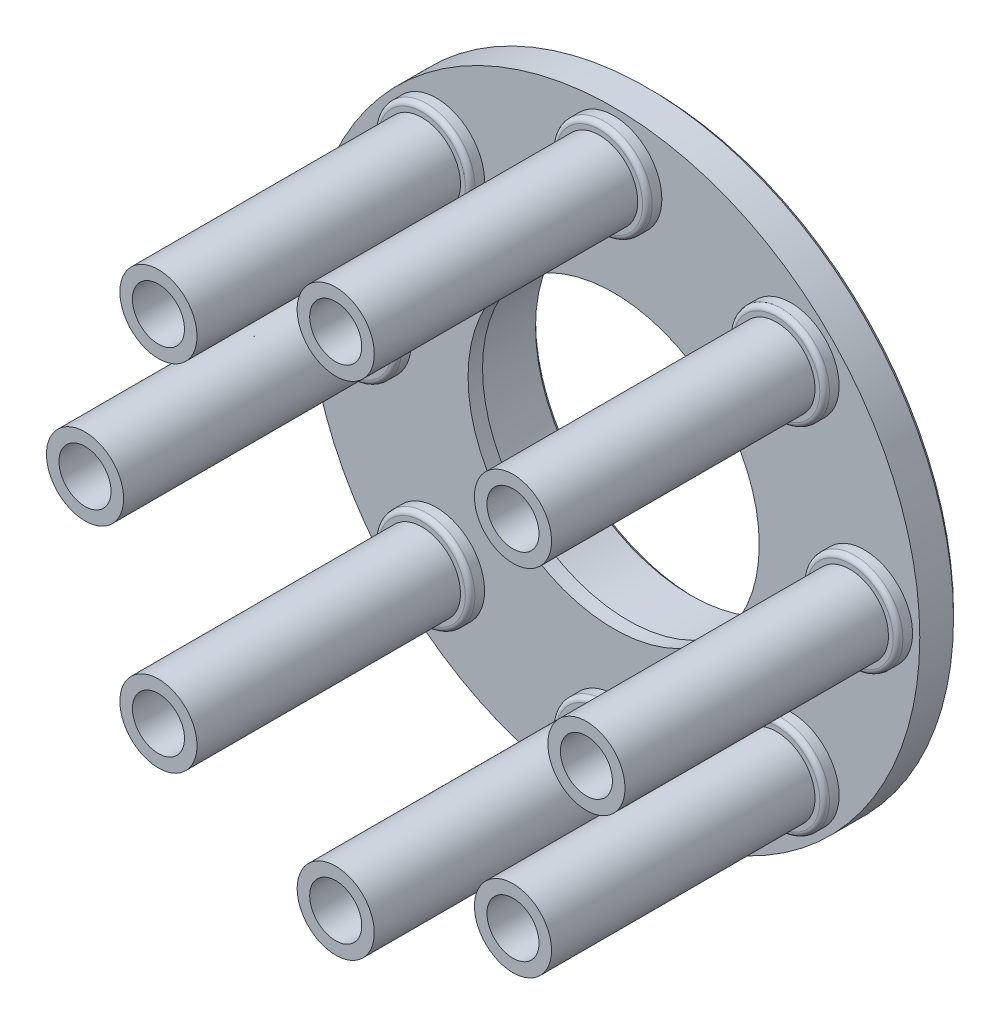
SolidWorks part; units mm, degrees
material "PLA"
ref_plane "Front Plane" through (0, 0, 0) normal (0, 0, 1) x (1, 0, 0)
ref_plane "Top Plane" through (0, 0, 0) normal (0, 1, 0) x (1, 0, 0)
ref_plane "Right Plane" through (0, 0, 0) normal (1, 0, 0) x (0, 0, -1)
sketch "Sketch1" plane through (0, 0, 0) normal (0, 0, 1) x (1, 0, 0)
  circle A0 centre (0, 0) radius 31.75
  circle A1 centre (0, 0) radius 26 construction
  circle A2 centre (0, 26) radius 2.7
  circle A3 centre (26, 0) radius 2.7
  circle A78 centre (0, -26) radius 2.7
  circle A79 centre (0, 26) radius 4.25 construction
  circle A80 centre (0, 0) radius 30.25 construction
  circle A87 centre (-26, 0) radius 2.7
  point P15 (0, 0)
  dimension "D2" = 52
  dimension "D3" = 5.4
  dimension "D5" = 8.5
  dimension "D1" = 1.5
  dimension "D4" = 4
extrude "Boss-Extrude1" add sketch "Sketch1" along normal blind 4
sketch "Sketch2" plane through (0, 0, 4) normal (0, 0, 1) x (1, 0, 0)
  circle A0 centre (0, 26) radius 4
  circle A2 centre (0, 26) radius 2.7 construction
  circle A5 centre (0, 26) radius 2.7
  point P15 (0, 0)
  dimension "D1" = 8
extrude "Boss-Extrude2" add sketch "Sketch2" along normal blind 28.8234
sketch "Sketch3" plane through (0, 0, 4) normal (0, 0, 1) x (1, 0, 0)
  arc A2 (5, 26) -> (5, 26) centre (0, 26) ccw
  circle A3 centre (0, 26) radius 5
  circle M5 centre (0, 26) radius 4
extrude "Boss-Extrude3" add sketch "Sketch3" along normal blind 1.5 contours A3 M5 region at (-4.8586, 26, 4)
sketch "Sketch4" plane through (0, 0, 4) normal (0, 0, 1) x (1, 0, 0)
  line L0 (0, 0) -> (-22.4506, 22.4506) construction
  line L1 (0, 0) -> (0, 26) construction
  circle A0 centre (0, 0) radius 31.75 construction
  circle A1 centre (0, 0) radius 31.75
  circle A2 centre (0, 26) radius 12 construction
  circle A6 centre (0, 0) radius 26 construction
  arc A8 (-13.189, 28.881) -> (-9.5294, 16.4375) centre (0, 26) ccw
  circle A9 centre (0, 0) radius 19
  circle A11 centre (0, 0) radius 14 construction
  arc A13 (-28.881, 13.189) -> (-16.4375, 9.5294) centre (-26, 0) cw
  circle A16 centre (0, 26) radius 13.5 construction
  point P15 (0, 0)
  point P25 (0, 0)
  dimension "D1" = 24
  dimension "D5" = 28
  dimension "D4" = 5
  dimension "D2" = 45
  dimension "D3" = 1.5
extrude "Boss-Extrude4" [suppressed] add sketch "Sketch4" along normal blind 28.8234 contours A1 A13 A9 A8
sketch "Sketch12" [suppressed] plane through (0, 0, 37.8382) normal (0, 0, 1) x (1, 0, 0)
  arc A0 (-11.2345, 15.816) -> (-15.816, 11.2345) centre (0, 0) ccw construction
  arc A1 (-11.2345, 15.816) -> (-15.816, 11.2345) centre (0, 0) ccw
  dimension "D1" = 6.4791
fillet "Fillet2" radius 0.5 1 edges at (5, 26, 5.5)
fillet "Fillet5" [suppressed] radius 1.6198
pattern_circular "CirPattern1" count 8 over 360 about axis through (0, 0, 4) along (0, 0, -1) of "Fillet2", "Boss-Extrude3", "Boss-Extrude2" reverse direction yes
ref_plane "Plane1" through (0, 0, 32.8234) normal (0, 0, 1) x (1, 0, 0)
chamfer "Chamfer1" distance 0.5 angle 45 1 edges at (31.75, 0, 0)
sketch "Sketch9" plane through (0, 0, 4) normal (0, 0, 1) x (1, 0, 0)
  circle A0 centre (0, 0) radius 8
  dimension "D1" = 16
extrude "Cut-Extrude4" cut sketch "Sketch9" against normal through all
sketch "Sketch10" plane through (0, 0, 0) normal (0, 0, -1) x (-1, 0, 0)
  circle A0 centre (0, 0) radius 8 construction
  circle A1 centre (0, 0) radius 8
  circle A2 centre (0, 0) radius 6.5
  dimension "D1" = 1.5
extrude "Boss-Extrude7" add sketch "Sketch10" against normal blind 6.5
sketch "Sketch13" plane through (0, 0, 0) normal (0, 1, 0) x (1, 0, 0)
  line L0 (0, 0) -> (0, -32.8234) construction
  line L1 (-4, -32.8234) -> (4, -32.8234) construction
  line L2 (15.6848, -4) -> (21.0848, -4) construction
  line L3 (-30, 0.5) -> (-38, -4) construction
  line L4 (-34.9404, -4) -> (-27.8293, 0)
  line L7 (31.25, 0) -> (-31.25, 0) construction
  line L8 (0, -4) -> (-38, -4) construction
  line L9 (-27.8293, 0) -> (-34.9404, 0)
  line L10 (-34.9404, 0) -> (-34.9404, -4)
  dimension "D1" = 30
  dimension "D2" = 38
  dimension "D3" = 4.5
  dimension "D4" = 1.5
sketch "Sketch14" plane through (0, 0, 4) normal (0, 0, 1) x (1, 0, 0)
  circle A0 centre (0, 0) radius 16.1
  circle A1 centre (0, 0) radius 6.5 construction
  dimension "D1" = 32.2
extrude "Cut-Extrude5" cut sketch "Sketch14" against normal through all both and the other way through all
sketch "Sketch15" plane through (0, 0, 4) normal (0, 0, 1) x (1, 0, 0)
  circle A0 centre (0, 0) radius 16.1
  circle A1 centre (0, 0) radius 15.1
  circle A2 centre (0, 0) radius 16.1 construction
  dimension "D1" = 1
extrude "Boss-Extrude8" add sketch "Sketch15" against normal blind 1.5
sketch "Sketch16" plane through (0, 0, 0) normal (0, 0, -1) x (-1, 0, 0)
  circle A0 centre (0, 0) radius 18.1
  circle A1 centre (0, 0) radius 16.1 construction
  circle M1 centre (0, 0) radius 16.1
extrude "Boss-Extrude9" add sketch "Sketch16" along normal blind 4.5 contours A0 M1 region at (17.5881, 0, 0)
chamfer "Chamfer3" distance 2 distance2 4.5 1 edges at (18.1, 0, 0) first distance on face at (18.1, 0, 0)
sketch "Sketch5" [suppressed] plane through (0, 0, 32.8234) normal (0, 0, 1) x (1, 0, 0)
  line L0 (0, 0) -> (-22.4506, 22.4506) construction
  line L1 (0, 0) -> (0, 26) construction
  circle A3 centre (-19.6222, 19.6222) radius 1.7
  circle A4 centre (0, 0) radius 31.75 construction
  arc A5 (-13.189, 28.881) -> (-28.881, 13.189) centre (0, 0) ccw construction
  dimension "D2" = 3.4
  dimension "D1" = 4
  dimension "D3" = 45
extrude "Cut-Extrude1" [suppressed] cut sketch "Sketch5" against normal through all
sketch "Sketch7" plane through (0, 0, 0) normal (0, 0, -1) x (-1, 0, 0)
  circle A0 centre (0, 26) radius 4.45
  circle A1 centre (0, 0) radius 26 construction
  point P15 (0, 0)
  dimension "D1" = 8.9
extrude "Cut-Extrude3" cut sketch "Sketch7" against normal blind 5 and the other way through all
sketch "Sketch6" [suppressed] plane through (0, 0, 0) normal (0, 0, -1) x (-1, 0, 0)
  circle A0 centre (19.6222, 19.6222) radius 2.95
  dimension "D1" = 5.9
extrude "Cut-Extrude2" [suppressed] cut sketch "Sketch6" against normal blind 3 and the other way through all
pattern_circular "CirPattern2" count 8 over 360 about axis through (0, 0, 4) along (0, 0, -1) of "Cut-Extrude3" reverse direction yes
chamfer "Chamfer4" distance 0.5 angle 45 1 edges at (-16.1, 0, -4.5)
equation "\"Nr_s\" = 132"
equation "\"module\" = 0.5"
equation "\"pressure_angle\" = 20.0"
equation "\"h_a\" = 0.5"
equation "\"h_f\" = 0.625"
equation "\"clr_tip_root\" = 0.125"
equation "\"dp_r_s\" = 66.0"
equation "\"db_r\"= \"dp_r_s\" * cos ( \"pressure_angle\" )'base CD"
equation "\"bearing_ID\" = 60"
equation "\"bearing_OD\" = 78"
equation "\"bearing_height\" = 10"
equation "\"clearance_planet\" = 1.5"
equation "\"case_dist\" = 6.5"
equation "\"Motor_case_OD_max\" = 111.3"
equation "\"case_mounting_PCD\" = 103.8"
equation "\"bearing mount thickness\" = 8"
equation "\"case_mounting_hole_dia\" = 3"
equation "\"output_mounting_PCD\" = 86"
equation "\"output_mounting_hole_dia\" = 4"
equation "\"clearance_case_mount_holes_shell_thickness\" = 1"
equation "\"motor_case_OD_base\" = 101.8"
equation "\"sec_carrier_thickness\" = 5"
equation "\"sun_coupler_hub_thickness\" = 4"
equation "\"clearance_sun_coupler_sec_carrier\" = 1.5"
equation "\"clearance_motor_and_case\" = 5"
equation "\"motor_OD\" = 86.8"
equation "\"Motor_case_thickness\" = 2.5"
equation "\"Motor_case_ID\" = 96.8"
equation "\"case_mounting_hole_shift\" = 1.0"
equation "\"output_mounting_nut_wrench_size\" = 7"
equation "\"output_mounting_nut_thickness\" = 3.2"
equation "\"case_mounting_hole_allen_socket_dia\" = 5.5"
equation "\"output_mounting_nut_depth\" = 3"
equation "\"case_mounting_bolt_depth\" = 4.5"
equation "\"Ns\" = 56"
equation "\"Np_b\" = 48"
equation "\"ring_radial_thickness\" = 5"
equation "\"ring_OD\"= \"Nr_s\" * \"module\" + \"ring_radial_thickness\" * 2"
equation "\"ring_to_chamfer_clearance\" = 1.5"
equation "\"Motor_case_OD_base_to_chamfer\" = 5"
equation "\"pattern_offset_from_motor_case_OD_base\" = 3"
equation "\"pattern_bulge_dia\" = 3"
equation "\"pattern_num_bulge\" = 18"
equation "\"pattern_depth\" = 2"
equation "\"motor_height\" = 26.5"
equation "\"case_mounting_wrench_size\" = 5.5"
equation "\"case_mounting_nut_clearance\" = 2"
equation "\"base_plate_thickness\" = 4"
equation "\"case_mounting_nut_thickness\" = 2.4"
equation "\"case_mounting_surface_height\" = 4"
equation "\"motor_mount_hole_PCD\" = 32"
equation "\"motor_mount_hole_dia\" = 4"
equation "\"motor_mount_hole_num\" = 4"
equation "\"central_hole_offset_from_motor_mount_PCD\" = 5"
equation "\"wire_slot_dist_from_center\" = 38"
equation "\"wire_slot_length\" = 10"
equation "\"wire_slot_radius\" = 2.5"
equation "\"driver_upper_holes_dist_from_center\" = 29"
equation "\"driver_lower_holes_dist_from_center\" = 13"
equation "\"driver_side_holes_dist_from_center\" = 22.5"
equation "\"driver_mount_holes_dia\" = 3"
equation "\"driver_mount_inserts_OD\" = 4.8"
equation "\"driver_mount_thickness\" = 1.5"
equation "\"driver_mount_height\" = 6"
equation "\"air_flow_hole_offset\" = 3"
equation "\"num_planet\" = 4"
equation "\"planet_pin_bolt_dia\" = 5"
equation "\"planet_pin_socket_head_dia\" = 8.5"
equation "\"carrier_PCD\" = 52.0"
equation "\"D2@Sketch1\"=\"carrier_PCD\""
equation "\"D3@Sketch1\"=\"planet_pin_bolt_dia\" + \"tight_clearance_3DP\""
equation "\"D4@Sketch1\"=\"num_planet\""
equation "\"D1@Boss-Extrude2\" = \"fw_p_s\" + \"clearance_planet\" * 2 + \"fw_p_b\""
equation "\"D1@Boss-Extrude3\"=\"clearance_planet\""
equation "\"D1@Sketch4\"=\"Np_b\"*\"module\""
equation "\"D3@Sketch4\"=\"clearance_planet\""
equation "\"D1@Boss-Extrude4\" = \"fw_p_s\" + \"clearance_planet\" * 2 + \"fw_p_b\""
equation "\"D1@Fillet2\"=\"clearance_planet\"/3"
equation "\"D1@CirPattern1\"=2*\"num_planet\""
equation "\"D1@CirPattern2\"=2*\"num_planet\""
equation "\"D1@Boss-Extrude7\"=\"bearing_height\"+ \"carrier_bearing_step_width\" - \"sun_shaft_bearing_width\""
equation "\"planet_shaft_dia\" = 8"
equation "\"D1@Sketch2\"= \"planet_shaft_dia\""
equation "\"planet_shaft_step_offset\" = 1"
equation "\"D1@Sketch3\"=\"planet_shaft_step_offset\""
equation "\"carrier_trapezoidal_support_sun_offset\" = 5"
equation "\"D4@Sketch4\"=\"carrier_trapezoidal_support_sun_offset\""
equation "\"carrier_trapezoidal_support_hole_PCD_offset_bearing_ID\" = 4"
equation "\"carrier_trapezoidal_support_hole_dia\" = 3"
equation "\"D2@Sketch5\"=\"carrier_trapezoidal_support_hole_dia\" + \"tight_clearance_3DP\""
equation "\"D1@Cut-Extrude2\"=\"carrier_trapezoidal_support_hole_dia\""
equation "\"carrier_trapezoidal_support_hole_socket_head_dia\" = 5.5"
equation "\"D1@Sketch6\"=\"carrier_trapezoidal_support_hole_socket_head_dia\" +  \"tight_clearance_3DP\""
equation "\"D1@Cut-Extrude3\"=\"planet_pin_bolt_dia\""
equation "\"D1@Sketch7\"=\"planet_pin_socket_head_dia\" + \"tight_clearance_3DP\""
equation "\"carrier_bearing_step_width\" = 1.5"
equation "\"standard_clearance_1_5mm\" = 1.5"
equation "\"standard_fillet_1_5mm\" = 1.5"
equation "\"sun_shaft_bearing_OD\" = 16"
equation "\"D1@Sketch9\"=\"sun_shaft_bearing_OD\""
equation "\"D1@Sketch10\"=\"standard_clearance_1_5mm\""
equation "\"sun_shaft_bearing_width\" = 5"
equation "\"standard_bearing_insertion_chamfer\" = 0.5"
equation "\"D1@Chamfer1\"=\"standard_bearing_insertion_chamfer\""
equation "\"D5@Sketch4\"=\"Ns\"*\"module\""
equation "\"D1@Sketch5\"=\"carrier_trapezoidal_support_hole_PCD_offset_bearing_ID\""
equation "\"D1@Plane1\" = \"fw_p_s\" + \"clearance_planet\" * 2 + \"fw_p_b\""
equation "\"D2@Sketch4\"=180/\"num_planet\""
equation "\"D3@Sketch5\"=180/\"num_planet\""
equation "\"carrier_trapezoidal_support_hole_wrench_size\" = 5.5"
equation "\"planet_pin_bolt_wrench_size\" = 8"
equation "\"pressure angle\" = 20.0"
equation "\"h_b\" = 0.625"
equation "\"dp_s\" = 28.0"
equation "\"db_s\" = 26.311393382005434"
equation "\"fw_s_calc\" = 2.7970255760332914"
equation "\"alpha_s\" = 0.8539582918412485"
equation "\"beta_s\" = 1.5063691306032174"
equation "\"dp_p_b\" = 24.0"
equation "\"db_p_b\" = 22.552622898861802"
equation "\"fw_p_s\" = 15.90536252346366"
equation "\"alpha_p_b\" = 0.8539582918412414"
equation "\"beta_p_b\" = 2.042083416317517"
equation "\"planet_bearing_OD\" = 12"
equation "\"planet_bearing_width\" = 3.5"
equation "\"planet_bore\" = 10"
equation "\"motor_output_hole_PCD\" = 23"
equation "\"motor_output_hole_dia\" = 4"
equation "\"motor_output_hole_num\" = 4"
equation "\"sun_shaft_bearing_ID\" = 8"
equation "\"sun_hub_dia\" = 30.0"
equation "\"sun_central_bolt_dia\" = 5"
equation "\"sun_central_bolt_socket_head_dia\" = 8.5"
equation "\"fw_s_used\" = 33.32338113475014"
equation "\"motor_output_hole_CSK_OD\" = 8"
equation "\"motor_output_hole_CSK_head_height\" = 2.0"
equation "\"bearing_retainer_thickness\" = 2"
equation "\"Np_s\" = 28"
equation "\"fw_p_b\" = 9.918018611286483"
equation "\"dp_p_s\" = 14.0"
equation "\"db_p_s\" = 13.155696691002717"
equation "\"alpha_p_s\" = 0.8539582918412485"
equation "\"beta_p_s\" = 4.720654844888932"
equation "\"D1@Fillet5\"= \"D1@Sketch12\" / 4"
equation "\"Nr_b\" = 152"
equation "\"dp_r_b\" = 76.0"
equation "\"db_r_b\" = 71.41663917972905"
equation "\"fw_r_b\" = 9.918018611286483"
equation "\"alpha_r_b\" = 0.8539582918412236"
equation "\"beta_r_b\" = 2.8921271099982366"
equation "\"ring_OD_b\" = 86.0"
equation "\"Fillet10\"= IIF ( \"ring_OD_b\" > ( \"bearing_OD\" + 2 * \"bearing mount thickness\" ) , \"suppressed\" , \"unsuppressed\" )"
equation "\"Fillet11\"= IIF ( \"ring_OD_b\" < ( \"bearing_OD\" + 2 * \"bearing mount thickness\" ) , \"suppressed\" , \"unsuppressed\" )"
equation "\"clr_tip_root_s\" = 0.125"
equation "\"db_r_s\" = 62.01971297186996"
equation "\"fw_r_s\" = 14.40536252346366"
equation "\"alpha_r_s\" = 0.8539582918412449"
equation "\"beta_r_s\" = 3.071552947318853"
equation "\"D1@Sketch13\"=\"bearing_ID\"/2"
equation "\"D2@Sketch13\"=(\"Nr_s\"*\"module\"+\"ring_radial_thickness\"*2)*0.5"
equation "\"D3@Sketch13\"=\"standard_clearance_1_5mm\"*3"
equation "\"D4@Sketch13\"=\"standard_clearance_1_5mm\""
equation "\"D5@Sketch1\"=\"planet_pin_socket_head_dia\""
equation "\"D1@Sketch1\"=\"standard_clearance_1_5mm\""
equation "\"small_ring_case_thickness\" = 4"
equation "\"carrier_thickness\" = 4"
equation "\"small_ring_output_wall_thickness\" = 5"
equation "\"small_ring_output_wall_to_bearing_shaft_attachement_hole_dia\" = 4"
equation "\"small_ring_output_wall_to_bearing_shaft_attachement_hole_depth\" = 6.5"
equation "\"small_ring_output_wall_to_bearing_shaft_attachement_nut_wrench\" = 7"
equation "\"small_ring_output_wall_to_bearing_shaft_attachement_nut_thickness\" = 3.2"
equation "\"small_ring_output_wall_to_bearing_shaft_attachement_hole_pcd\" = 12"
equation "\"small_ring_output_wall_to_bearing_shaft_attachement_hole_num\" = 3"
equation "\"small_ring_output_wall_to_bearing_shaft_attachement_hole_CSK_OD\" = 8"
equation "\"small_ring_output_wall_to_bearing_shaft_attachement_hole_CSK_head_height\" = 2.0"
equation "\"carrier_small_ring_inner_bearing_ID\" = 20"
equation "\"carrier_small_ring_inner_bearing_OD\" = 32"
equation "\"carrier_small_ring_inner_bearing_height\" = 7"
equation "\"carrier_small_ring_inner_bearing_flap\" = 2"
equation "\"gear_casing_big_ring_to_bearing_dist\" = 24.90536252346366"
equation "\"gear_casing_thickness\" = 4"
equation "\"D1@Boss-Extrude1\"=\"carrier_thickness\""
equation "\"D1@Boss-Extrude9\"= \"carrier_small_ring_inner_bearing_height\" - \"carrier_thickness\" + \"standard_clearance_1_5mm\""
equation "\"D3@Chamfer3\"=\"carrier_small_ring_inner_bearing_height\"-\"carrier_thickness\" + \"standard_clearance_1_5mm\""
equation "\"D1@Chamfer3\"=\"standard_clearance_1_5mm\"*4/3"
equation "\"D1@Sketch14\"=\"carrier_small_ring_inner_bearing_OD\" + \"tight_clearance_3DP\"/2"
equation "\"D1@Sketch16\"=\"standard_clearance_1_5mm\"*4/3"
equation "\"tight_clearance_3DP\"= 0.4"
equation "\"loose_clearance_3DP\"= 0.8"
equation "\"D1@Chamfer4\"= \"standard_bearing_insertion_chamfer\""
